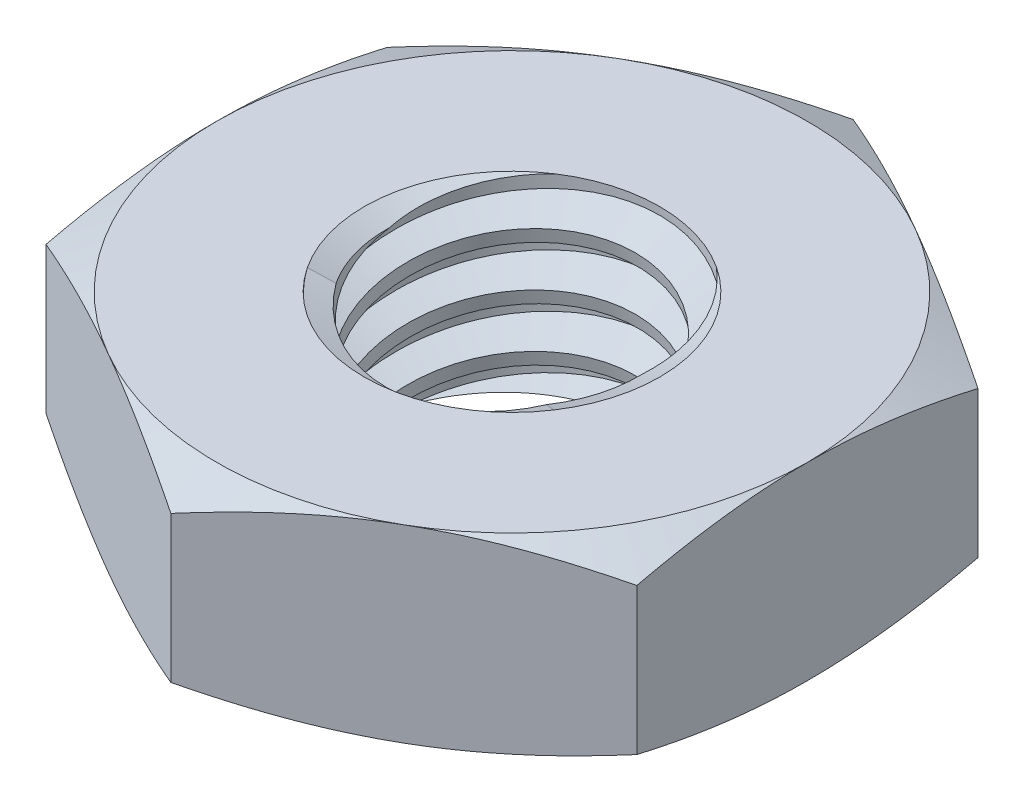
SolidWorks part; units mm, degrees
ref_plane "Front" through (0, 0, 0) normal (0, 0, 1) x (1, 0, 0)
ref_plane "Top" through (0, 0, 0) normal (0, 1, 0) x (1, 0, 0)
ref_plane "Right" through (0, 0, 0) normal (1, 0, 0) x (0, 0, -1)
sketch "Sketch1" plane through (0, 0, 0) normal (0, 1, 0) x (1, 0, 0)
  line L1 (0, 2.8868) -> (-2.5, 1.4434)
  line L2 (-2.5, 1.4434) -> (-2.5, -1.4434)
  line L3 (-2.5, -1.4434) -> (0, -2.8868)
  line L4 (0, -2.8868) -> (2.5, -1.4434)
  line L5 (2.5, -1.4434) -> (2.5, 1.4434)
  line L6 (2.5, 1.4434) -> (0, 2.8868)
  circle A0 centre (0, 0) radius 2.5 construction
  dimension "Hex Flats" = 5
extrude "Extrude1" add sketch "Sketch1" along normal mid plane 1.6
sketch "Sketch2" plane through (0, 0, 0) normal (1, 0, 0) x (0, 0, -1)
  line L0 (-1.25, -0.8) -> (-1.25, 0.8) construction
  line L1 (0, -0.8) -> (1.25, -0.8)
  line L2 (0, -0.8) -> (0, 0.8)
  line L3 (0, 0.8) -> (1.25, 0.8)
  line L4 (1.25, -0.8) -> (1.25, 0.8)
  line L5 (-1.4434, 0.8) -> (1.4434, 0.8) construction
  line L6 (-1.4434, -0.8) -> (1.4434, -0.8) construction
  line L7 (0, -2.05) -> (0, -0.8) construction
  dimension "Thread Dia" = 2.5
revolve "Revolve1" add sketch "Sketch2" angle 360 about L7
sketch "Sketch3" plane through (0, 0, 0) normal (1, 0, 0) x (0, 0, -1)
  line L0 (1.25, 0.8) -> (-1.25, 0.8) construction
  line L1 (-1.25, 0.8) -> (-1.25, 0.35) construction
  line L2 (-1.25, 0.35) -> (1.25, 0.8) construction
  line L3 (1.25, 0.8) -> (1.26, 0.7446) construction
  line L4 (1.26, 0.7446) -> (1.3297, 0.3571)
  line L5 (1.3297, 0.3571) -> (1.0651, 0.4524)
  line L6 (1.0651, 0.4524) -> (1.0452, 0.5631)
  line L7 (1.0452, 0.5631) -> (1.26, 0.7446)
  line L8 (1.0551, 0.5077) -> (1.2948, 0.5509) construction
  line L9 (1.25, 0.8) -> (1.25, 0.5428) construction
  line L10 (1.25, 0.5428) -> (-1.25, 0.0928) construction
  line L11 (-1.25, 0.0928) -> (-1.25, 0.35) construction
  line L12 (-0.0868, 0.8) -> (0.0868, -0.1644) construction
  line L13 (-1.25, -0.8) -> (-1.25, 0.8) construction
  line L14 (0, 0.8) -> (1.25, 0.8) construction
  line L15 (1.25, -0.8) -> (1.25, 0.8) construction
  line L16 (0, 0) -> (0, 0.8) construction
  line L17 (-1.26, 0.7446) -> (-1.3297, 0.3571) construction
  line L18 (-1.0452, 0.5631) -> (-1.26, 0.7446) construction
  line L19 (-1.0651, 0.4524) -> (-1.0452, 0.5631) construction
  line L20 (-1.3297, 0.3571) -> (-1.0651, 0.4524) construction
  line L21 (0.0868, 0.8) -> (-0.0868, -0.1644) construction
  point P13 (0, 0.3178)
  dimension "D1" = 0.0563
  dimension "D2" = 0.1125
  dimension "Thread Pitch" = 0.45
  dimension "D4" = 60
  dimension "D5" = 0.45
revolve "Cut-Revolve1" cut sketch "Sketch3" angle 360 about L12
pattern_linear "LPattern1" count 4 spacing 0.45 along (0, -1, 0) count 2 spacing 0.45 along (0, 1, 0) of "Cut-Revolve1"
sketch "Sketch4" plane through (0, 0, 0) normal (1, 0, 0) x (0, 0, -1)
  line L0 (0, 0.8) -> (1.25, 0.8)
  line L1 (1.25, 0.8) -> (1.0452, 0.7045)
  line L2 (1.0452, 0.7045) -> (1.0452, -0.7045)
  line L3 (1.0452, -0.7045) -> (1.25, -0.8)
  line L4 (1.25, -0.8) -> (0, -0.8)
  line L5 (0, -0.8) -> (0, 0.8)
  line L6 (1.25, -0.8) -> (1.25, 0.8) construction
  line L7 (0, 0.8) -> (1.25, 0.8) construction
  line L8 (0, -0.8) -> (1.25, -0.8) construction
  line L9 (0, -0.8) -> (0, 0.8) construction
  line L10 (0, 0.8) -> (0, 1.026) construction
  dimension "D1" = 25
revolve "Cut-Revolve2" cut sketch "Sketch4" angle 360 about L10
combine bodies "Combine1" operation type subtract main body 112 bodies to subtract 111
sketch "Sketch5" plane through (0, 0, 0) normal (1, 0, 0) x (0, 0, -1)
  line L0 (0, -0.8) -> (2.5, -0.8)
  line L1 (2.5, -0.8) -> (2.8868, -0.6197)
  line L2 (2.8868, -0.6197) -> (2.8868, 0.6197)
  line L3 (2.8868, 0.6197) -> (2.5, 0.8)
  line L4 (0, 0.8) -> (0, 2.07)
  line L5 (0, 2.07) -> (4.1568, 2.07)
  line L6 (4.1568, 2.07) -> (4.1568, -2.07)
  line L7 (4.1568, -2.07) -> (0, -2.07)
  line L8 (0, -2.07) -> (0, -0.8)
  line L9 (2.5, 0.8) -> (2.5, -0.8) construction
  line L11 (0, -0.8) -> (1.25, -0.8) construction
  line L12 (2.5, 0.8) -> (0, 0.8)
  line L13 (2.8868, 0) -> (4.1568, 0) construction
  line L14 (2.8868, 0.8) -> (2.8868, -0.8) construction
  line L15 (0, -0.8) -> (0, 0.8) construction
  line L17 (0, 0) -> (2.5, 0) construction
  line L22 (0, 0.8) -> (1.25, 0.8) construction
  dimension "D1" = 25
  dimension "D2" = 1.27
  dimension "D3" = 1.6
revolve "Cut-Revolve3" cut sketch "Sketch5" angle 360 about L15
equation "\"D1@Sketch3\"=\"Thread Pitch@Sketch3\"/8"
equation "\"D2@Sketch3\"=\"Thread Pitch@Sketch3\"/4"
equation "\"D5@Sketch3\"=\"Thread Pitch@Sketch3\""
equation "\"D4@LPattern1\"=\"Thread Pitch@Sketch3\""
equation "\"D3@LPattern1\"=\"Thread Pitch@Sketch3\""
equation "\"D1@LPattern1\"=\"Height@Extrude1\"/\"Thread Pitch@Sketch3\""
